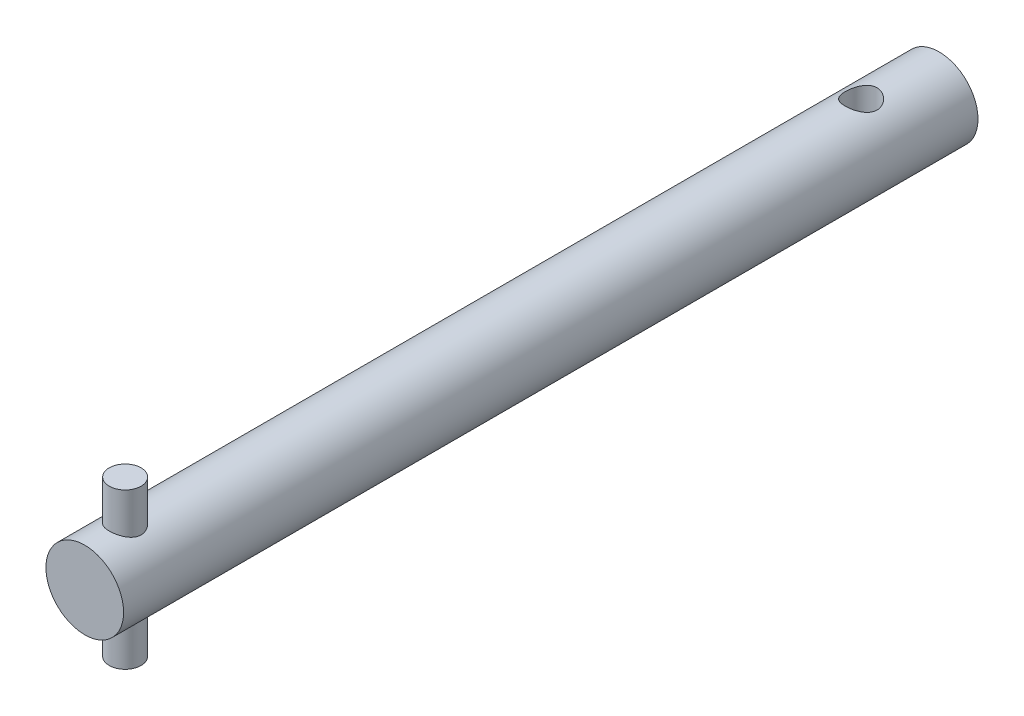
SolidWorks part; units mm, degrees
ref_plane "Спереди" through (0, 0, 0) normal (0, 0, 1) x (1, 0, 0)
ref_plane "Сверху" through (0, 0, 0) normal (0, 1, 0) x (1, 0, 0)
ref_plane "Справа" through (0, 0, 0) normal (1, 0, 0) x (0, 0, -1)
sketch "Эскиз1" plane through (0, 0, 0) normal (0, 0, 1) x (1, 0, 0)
  circle A0 centre (0, 0) radius 10
  dimension "D2" = 20
extrude "Бобышка-Вытянуть1" add sketch "Эскиз1" along normal blind 220
sketch "Эскиз2" plane through (0, 0, 0) normal (0, 1, 0) x (1, 0, 0)
  line L1 (10, 0) -> (-10, 0) construction
  line L4 (-10, -220) -> (10, -220) construction
  circle A0 centre (0, -20.1) radius 4.1
  circle A1 centre (0, -209.6) radius 4.1
  dimension "D1" = 8.2
  dimension "D3" = 6.3
  dimension "D2" = 16
extrude "Вырез-Вытянуть1" cut sketch "Эскиз2" against normal through all both and the other way through all
sketch "Эскиз3" plane through (0, 0, 0) normal (0, 1, 0) x (1, 0, 0)
  circle A0 centre (0, -209.6) radius 4.1
extrude "Бобышка-Вытянуть2" add sketch "Эскиз3" along normal blind 20 and the other way blind 20 separate body
